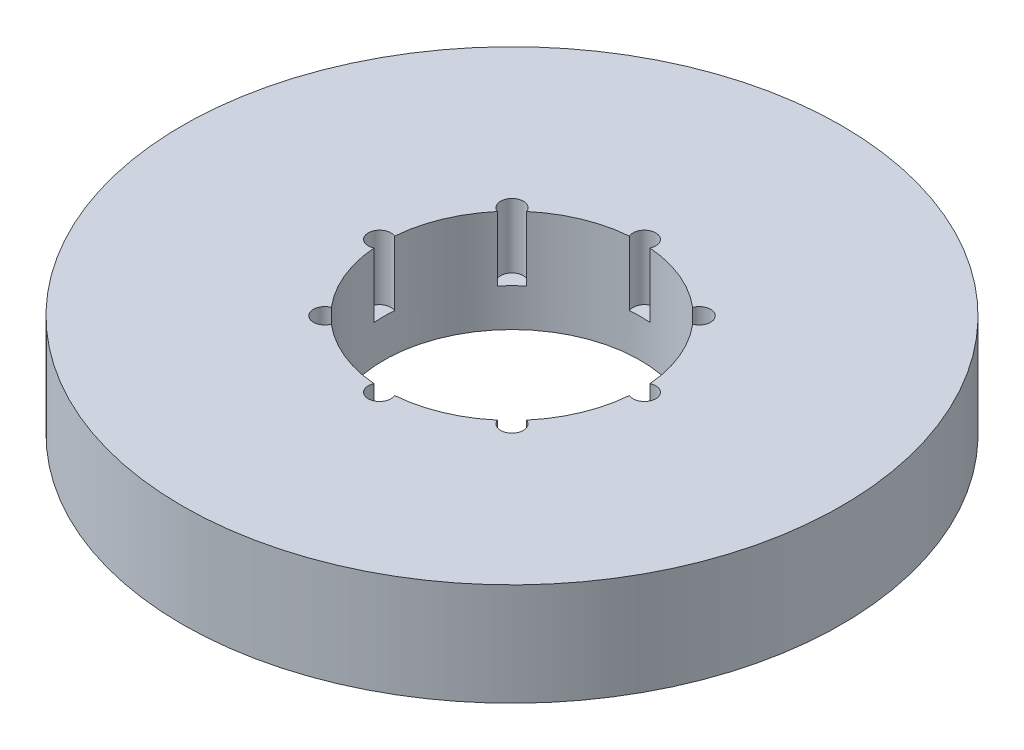
SolidWorks part; units mm, degrees
ref_plane "Front Plane" through (0, 0, 0) normal (0, 0, 1) x (1, 0, 0)
ref_plane "Top Plane" through (0, 0, 0) normal (0, 1, 0) x (1, 0, 0)
ref_plane "Right Plane" through (0, 0, 0) normal (1, 0, 0) x (0, 0, -1)
sketch "Sketch1" plane through (0, 0, 0) normal (0, 1, 0) x (1, 0, 0)
  circle A0 centre (0, 0) radius 90
  dimension "FLANGE_OD" = 180
extrude "Boss-Extrude1" add sketch "Sketch1" along normal blind 28
sketch "Sketch2" plane through (0, 0, 0) normal (0, 1, 0) x (1, 0, 0)
  circle A0 centre (0, 0) radius 35
  dimension "BORE_D" = 70
extrude "Cut-Extrude1" cut sketch "Sketch2" along normal through all
sketch "Sketch3" plane through (0, 28, 0) normal (0, 1, 0) x (1, 0, 0)
  circle A0 centre (0, 0) radius 36.1619 construction
  circle A1 centre (-36.1619, 0) radius 3.0893
  dimension "BOLT_D" = 6.1786
  dimension "BOLT_PCD" = 72.3237
extrude "Cut-Extrude2" cut sketch "Sketch3" against normal blind 17.6247
pattern_circular "CirPattern1" count 8 over 360 about axis through (0, 0, 0) along (0, 1, 0) of "Cut-Extrude2"
